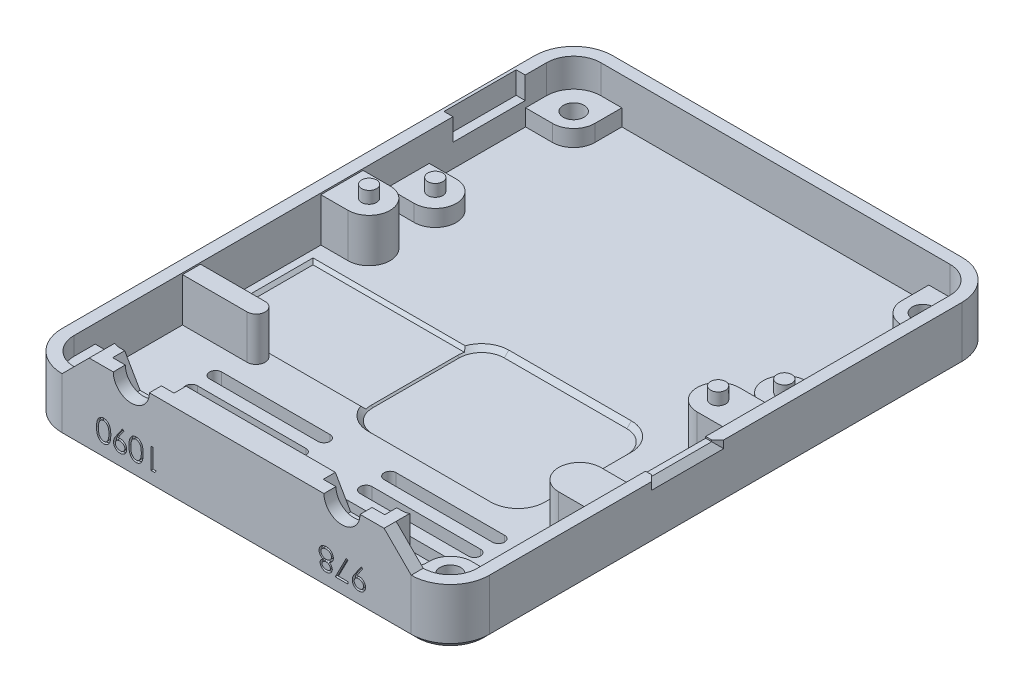
SolidWorks part; units mm, degrees
ref_plane "Front Plane" through (0, 0, 0) normal (0, 0, 1) x (1, 0, 0)
ref_plane "Top Plane" through (0, 0, 0) normal (0, 1, 0) x (1, 0, 0)
ref_plane "Right Plane" through (0, 0, 0) normal (1, 0, 0) x (0, 0, -1)
sketch "Sketch1" plane through (0, 0, 0) normal (0, 1, 0) x (1, 0, 0)
  line L0 (-33.8462, -25.5532) -> (31.1538, -25.5532)
  line L1 (-33.8462, 38.4468) -> (31.1538, 38.4468)
  line L2 (-33.8462, 38.4468) -> (-33.8462, 8.4468)
  line L3 (-33.8462, 8.4468) -> (31.1538, 8.4468)
  line L4 (31.1538, 38.4468) -> (31.1538, 8.4468)
  line L5 (-30.3462, 34.9468) -> (27.6538, 34.9468)
  line L6 (-30.3462, 34.9468) -> (-30.3462, 11.9468)
  line L7 (-30.3462, 11.9468) -> (27.6538, 11.9468)
  line L8 (27.6538, 34.9468) -> (27.6538, 11.9468)
  line L9 (-30.3462, 0.9468) -> (27.6538, 0.9468)
  line L10 (-30.3462, 0.9468) -> (-30.3462, -22.0532)
  line L11 (-33.8462, 4.4468) -> (31.1538, 4.4468)
  line L12 (-33.8462, 4.4468) -> (-33.8462, -25.5532)
  line L13 (-30.3462, -22.0532) -> (27.6538, -22.0532)
  line L14 (31.1538, 4.4468) -> (31.1538, -25.5532)
  line L15 (27.6538, 0.9468) -> (27.6538, -22.0532)
  line L16 (-37.9161, 25.3468) -> (-35.3276, 25.3468)
  line L17 (7.5538, 7.5472) -> (7.5538, 6.2645)
  line L18 (20.1538, 7.5472) -> (20.1538, 6.2645)
  dimension "D1" = 65
  dimension "D2" = 30
  dimension "D3" = 58
  dimension "D4" = 23
  dimension "D5" = 3.5
  dimension "D6" = 3.5
  dimension "D7" = 65
  dimension "D8" = 30
  dimension "D9" = 58
  dimension "D10" = 23
  dimension "D11" = 3.5
  dimension "D12" = 3.5
  dimension "D13" = 4
  dimension "D14" = 16.9
  dimension "D15" = 41.4
  dimension "D16" = 54
sketch "Sketch2" plane through (0, 0, 0) normal (0, 1, 0) x (1, 0, 0)
  line L0 (-33.8462, 38.4468) -> (-33.8462, 8.4468) construction
  line L1 (-30.3462, 39.4468) -> (27.6538, 39.4468)
  line L2 (-34.8462, 34.9468) -> (-34.8462, -43.5532)
  line L3 (-30.3462, -48.0532) -> (27.6538, -48.0532)
  line L4 (32.1538, 34.9468) -> (32.1538, -43.5532)
  line L5 (-33.8462, 38.4468) -> (31.1538, 38.4468) construction
  line L6 (31.1538, 38.4468) -> (31.1538, 8.4468) construction
  line L7 (-30.3462, 41.4468) -> (27.6538, 41.4468)
  line L8 (34.1538, 34.9468) -> (34.1538, -43.5532)
  line L9 (-30.3462, -50.0532) -> (27.6538, -50.0532)
  line L10 (-36.8462, 34.9468) -> (-36.8462, -43.5532)
  line L11 (-34.8462, 39.4468) -> (32.1538, 39.4468) construction
  line L12 (-34.8462, 39.4468) -> (-34.8462, -48.0532) construction
  line L13 (-36.8462, 41.4468) -> (-36.8462, -50.0532) construction
  line L14 (-36.8462, 41.4468) -> (34.1538, 41.4468) construction
  line L15 (32.1538, 39.4468) -> (32.1538, -48.0532) construction
  line L16 (34.1538, 41.4468) -> (34.1538, -50.0532) construction
  line L17 (-36.8462, -50.0532) -> (34.1538, -50.0532) construction
  line L18 (-34.8462, -48.0532) -> (32.1538, -48.0532) construction
  arc A0 (-30.3462, 39.4468) -> (-34.8462, 34.9468) centre (-30.3462, 34.9468) ccw
  arc A1 (-36.8462, 34.9468) -> (-30.3462, 41.4468) centre (-30.3462, 34.9468) cw
  arc A2 (32.1538, 34.9468) -> (27.6538, 39.4468) centre (27.6538, 34.9468) ccw
  arc A3 (34.1538, 34.9468) -> (27.6538, 41.4468) centre (27.6538, 34.9468) ccw
  arc A4 (27.6538, -50.0532) -> (34.1538, -43.5532) centre (27.6538, -43.5532) ccw
  arc A5 (-36.8462, -43.5532) -> (-30.3462, -50.0532) centre (-30.3462, -43.5532) ccw
  arc A6 (27.6538, -48.0532) -> (32.1538, -43.5532) centre (27.6538, -43.5532) ccw
  arc A7 (-30.3462, -48.0532) -> (-34.8462, -43.5532) centre (-30.3462, -43.5532) cw
  dimension "D6" = 4.5
  dimension "D7" = 6.5
  dimension "D8" = 4.5
  dimension "D9" = 6.5
  dimension "D10" = 6.5
  dimension "D11" = 4.5
  dimension "D1" = 1
  dimension "D2" = 1
  dimension "D3" = 1
  dimension "D4" = 87.5
  dimension "D5" = 2
extrude "Boss-Extrude1" add sketch "Sketch2" along normal blind 9.5
sketch "Sketch3" plane through (0, 0, 0) normal (0, 1, 0) x (1, 0, 0)
  line L0 (-30.3462, -48.0532) -> (27.6538, -48.0532)
  line L1 (-30.3462, 39.4468) -> (27.6538, 39.4468)
  line L2 (-34.8462, 34.9468) -> (-34.8462, -43.5532)
  line L4 (32.1538, 34.9468) -> (32.1538, -43.5532)
  arc A0 (-34.8462, -43.5532) -> (-30.3462, -48.0532) centre (-30.3462, -43.5532) ccw
  arc A1 (27.6538, -48.0532) -> (32.1538, -43.5532) centre (27.6538, -43.5532) ccw
  arc A2 (32.1538, 34.9468) -> (27.6538, 39.4468) centre (27.6538, 34.9468) ccw
  arc A3 (-30.3462, 39.4468) -> (-34.8462, 34.9468) centre (-30.3462, 34.9468) ccw
  dimension "D1" = 4.5
  dimension "D2" = 4.5
  dimension "D3" = 87.5
extrude "Boss-Extrude2" add sketch "Sketch3" along normal blind 2
sketch "Sketch4" plane through (0, 2, 0) normal (0, 1, 0) x (1, 0, 0)
  line L1 (-4.1234, -3.5548) -> (16.2444, -3.5548)
  line L2 (-7.1234, -6.5548) -> (-7.1234, -20.9191)
  line L3 (-4.1234, -23.9191) -> (16.2444, -23.9191)
  line L4 (19.2444, -6.5548) -> (19.2444, -20.9191)
  arc A0 (16.2444, -23.9191) -> (19.2444, -20.9191) centre (16.2444, -20.9191) ccw
  arc A1 (-7.1234, -20.9191) -> (-4.1234, -23.9191) centre (-4.1234, -20.9191) ccw
  arc A2 (19.2444, -6.5548) -> (16.2444, -3.5548) centre (16.2444, -6.5548) ccw
  arc A3 (-7.1234, -6.5548) -> (-4.1234, -3.5548) centre (-4.1234, -6.5548) cw
  dimension "D1" = 3
extrude "Cut-Extrude2" cut sketch "Sketch4" against normal blind 0.75
chamfer "Chamfer1" distance 1.5 angle 45 8 edges at (6.0605, 2, 23.9191) (18.3657, 2, 23.0404) (-6.2447, 2, 23.0404) (19.2444, 2, 13.7369) (-7.1234, 2, 13.7369) (18.3657, 2, 4.4335) (-6.2447, 2, 4.4335) (6.0605, 2, 3.5548) tangent propagation no
sketch "Sketch5" plane through (0, 1.25, 0) normal (0, 1, 0) x (1, 0, 0)
  line L0 (-30.3462, 4.4468) -> (-34.8462, 4.4468)
  line L1 (-34.8462, 34.9468) -> (-34.8462, -43.5532) construction
  line L2 (-34.8462, 4.4468) -> (-34.8462, -2.5532)
  line L3 (-34.8462, -2.5532) -> (-30.3462, -2.5532)
  line L4 (27.6538, 4.4468) -> (32.1538, 4.4468)
  line L5 (32.1538, -43.5532) -> (32.1538, 34.9468) construction
  line L6 (32.1538, 4.4468) -> (32.1538, -2.5532)
  line L7 (32.1538, -43.5532) -> (32.1538, 34.9468) construction
  line L8 (32.1538, -2.5532) -> (27.6538, -2.5532)
  line L9 (32.1538, -18.5532) -> (32.1538, -25.5532)
  line L10 (-34.8462, -25.5532) -> (-24.1094, -25.5532)
  line L11 (-34.8462, -25.5532) -> (-34.8462, -22.5532)
  line L12 (-34.8462, -22.5532) -> (-24.1094, -22.5532)
  line L13 (32.1538, -25.5532) -> (27.6538, -25.5532)
  line L14 (27.6538, -18.5532) -> (32.1538, -18.5532)
  arc A0 (-30.3462, -2.5532) -> (-30.3462, 4.4468) centre (-30.3462, 0.9468) ccw
  arc A1 (27.6538, 4.4468) -> (27.6538, -2.5532) centre (27.6538, 0.9468) ccw
  arc A2 (-24.1094, -22.5532) -> (-24.1094, -25.5532) centre (-24.1094, -24.0532) cw
  arc A3 (27.6538, -18.5532) -> (27.6538, -25.5532) centre (27.6538, -22.0532) ccw
  dimension "D1" = 3
extrude "Boss-Extrude3" add sketch "Sketch5" along normal blind 8
sketch "Sketch6" plane through (0, 1.25, 0) normal (0, 1, 0) x (1, 0, 0)
  line L0 (-30.3462, 15.4468) -> (-34.8462, 15.4468)
  line L1 (-34.8462, 34.9468) -> (-34.8462, -43.5532) construction
  line L2 (-34.8462, 15.4468) -> (-34.8462, 8.4468)
  line L3 (-34.8462, 34.9468) -> (-34.8462, 4.4468) construction
  line L4 (-34.8462, 8.4468) -> (-30.3462, 8.4468)
  line L5 (-26.8462, 34.9468) -> (-26.8462, 39.4468)
  line L6 (27.6538, 39.4468) -> (-30.3462, 39.4468) construction
  line L7 (-26.8462, 39.4468) -> (-30.3462, 39.4468)
  line L8 (-30.3462, 31.4468) -> (-34.8462, 31.4468)
  line L9 (-34.8462, 31.4468) -> (-34.8462, 34.9468)
  line L10 (24.1538, 34.9468) -> (24.1538, 39.4468)
  line L11 (24.1538, 39.4468) -> (27.6538, 39.4468)
  line L12 (27.6538, 31.4468) -> (32.1538, 31.4468)
  line L13 (32.1538, 4.4468) -> (32.1538, 34.9468) construction
  line L14 (32.1538, 31.4468) -> (32.1538, 34.9468)
  line L15 (27.6538, 15.4468) -> (32.1538, 15.4468)
  line L16 (27.6538, 8.4468) -> (32.1538, 8.4468)
  line L17 (32.1538, -43.5532) -> (32.1538, 34.9468) construction
  line L18 (32.1538, 8.4468) -> (32.1538, 15.4468)
  arc A0 (-30.3462, 31.4468) -> (-26.8462, 34.9468) centre (-30.3462, 34.9468) ccw
  arc A1 (24.1538, 34.9468) -> (27.6538, 31.4468) centre (27.6538, 34.9468) ccw
  arc A2 (27.6538, 15.4468) -> (27.6538, 8.4468) centre (27.6538, 11.9468) ccw
  arc A3 (-30.3462, 8.4468) -> (-30.3462, 15.4468) centre (-30.3462, 11.9468) ccw
  arc A4 (-30.3462, 39.4468) -> (-34.8462, 34.9468) centre (-30.3462, 34.9468) ccw
  arc A5 (32.1538, 34.9468) -> (27.6538, 39.4468) centre (27.6538, 34.9468) ccw
  dimension "D1" = 4.5
  dimension "D2" = 4.5
extrude "Boss-Extrude4" add sketch "Sketch6" along normal blind 3.5
sketch "Sketch7" plane through (0, 0, 50.0532) normal (0, 0, 1) x (1, 0, 0)
  line L0 (27.6538, 9.5) -> (-30.3462, 9.5)
  line L3 (13.1538, 14) -> (-15.8462, 14)
  line L4 (-1.3462, 9.5) -> (-1.3462, 14) construction
  line L5 (-30.3462, 9.5) -> (27.6538, 9.5) construction
  line L6 (-30.3462, 9.5) -> (-25.8462, 14)
  line L7 (-25.8462, 14) -> (-21.8462, 14)
  line L9 (23.1538, 14) -> (19.1538, 14)
  line L13 (27.6538, 9.5) -> (23.1538, 14)
  arc A0 (-21.8462, 14) -> (-15.8462, 14) centre (-18.8462, 14) ccw
  arc A1 (13.1538, 14) -> (19.1538, 14) centre (16.1538, 14) ccw
  dimension "D2" = 35
  dimension "D1" = 4.5
  dimension "D6" = 3
  dimension "D7" = 3
  dimension "D3" = 4.5
  dimension "D4" = 45
  dimension "D5" = 4.5
extrude "Boss-Extrude5" add sketch "Sketch7" against normal up to vertex (2 mm away) up to point (-30.3462, 9.5, 48.0532)
sketch "Sketch10" plane through (0, 2, 0) normal (0, 1, 0) x (1, 0, 0)
  line L0 (-30.3462, -40.0532) -> (-34.8462, -40.0532)
  line L1 (27.6538, -40.0532) -> (32.1538, -40.0532)
  line L2 (-34.8462, -40.0532) -> (-34.8462, -43.5532)
  line L3 (-26.8462, -43.5532) -> (-26.8462, -48.0532)
  line L4 (32.1538, -43.5532) -> (32.1538, 34.9468) construction
  line L5 (-26.8462, -48.0532) -> (-30.3462, -48.0532)
  line L6 (32.1538, -40.0532) -> (32.1538, -43.5532)
  line L7 (24.1538, -43.5532) -> (24.1538, -48.0532)
  line L8 (-30.3462, -48.0532) -> (27.6538, -48.0532) construction
  line L9 (24.1538, -48.0532) -> (27.6538, -48.0532)
  line L10 (-4.8462, -43.5532) -> (-4.8462, -48.0532)
  line L11 (-4.8462, -48.0532) -> (2.1538, -48.0532)
  line L12 (2.1538, -48.0532) -> (2.1538, -43.5532)
  arc A0 (-34.8462, -43.5532) -> (-30.3462, -48.0532) centre (-30.3462, -43.5532) ccw
  arc A1 (-26.8462, -43.5532) -> (-30.3462, -40.0532) centre (-30.3462, -43.5532) ccw
  arc A2 (32.1538, -43.5532) -> (27.6538, -48.0532) centre (27.6538, -43.5532) cw
  arc A3 (27.6538, -48.0532) -> (32.1538, -43.5532) centre (27.6538, -43.5532) ccw construction
  arc A4 (27.6538, -40.0532) -> (24.1538, -43.5532) centre (27.6538, -43.5532) ccw
  arc A5 (2.1538, -43.5532) -> (-4.8462, -43.5532) centre (-1.3462, -43.5532) ccw
extrude "Boss-Extrude6" add sketch "Sketch10" along normal offset from surface (4.5 mm away) 3 up to face at (-1.3462, 9.5, 4.3032)
sketch "Sketch11" plane through (34.1538, 0, 0) normal (1, 0, 0) x (0, 0, -1)
  line L1 (-15.6251, 10.2426) -> (-5.6251, 10.2426)
  line L2 (-15.6251, 10.2426) -> (-15.6251, 9.2424)
  line L3 (-15.6251, 9.2424) -> (-5.6251, 9.2424)
  line L4 (-5.6251, 10.2426) -> (-5.6251, 9.2424)
extrude "Cut-Extrude3" cut sketch "Sketch11" against normal up to next
chamfer "Chamfer2" distance 1 angle 45 3 edges at (34.1538, 9.3712, 5.6251) (34.1538, 9.3712, 15.6251) (34.1538, 9.2424, 10.6251)
sketch "Sketch12" plane through (-34.8462, 0, 0) normal (-1, 0, 0) x (0, 0, 1)
  line L1 (-31.3918, 9.8223) -> (-19.3918, 9.8223)
  line L2 (-31.3918, 9.8223) -> (-31.3918, 5.8223)
  line L3 (-31.3918, 5.8223) -> (-19.3918, 5.8223)
  line L4 (-19.3918, 9.8223) -> (-19.3918, 5.8223)
  line L5 (-31.3918, 9.8223) -> (-19.3918, 5.8223) construction
  line L6 (-31.3918, 5.8223) -> (-19.3918, 9.8223) construction
  point P0 (-25.3918, 7.8223)
  dimension "D1" = 12
  dimension "D2" = 4
chamfer "Chamfer4" distance 1 angle 45 8 edges at (34.1538, 0, 4.3032) (32.25, 0, -39.543) (32.25, 0, 48.1493) (-1.3462, 0, -41.4468) (-1.3462, 0, 50.0532) (-34.9423, 0, -39.543) (-34.9423, 0, 48.1493) (-36.8462, 0, 4.3032)
sketch "Sketch34" plane through (0, 2, 0) normal (0, 1, 0) x (1, 0, 0)
  line L1 (-5.843, -6.5548) -> (-32.1578, -6.5548)
  line L2 (-5.843, -6.5548) -> (-5.843, -20.9191)
  line L3 (-5.843, -20.9191) -> (-32.1578, -20.9191)
  line L4 (-32.1578, -6.5548) -> (-32.1578, -20.9191)
extrude "Cut-Extrude5" cut sketch "Sketch34" against normal blind 0.5
chamfer "Chamfer5" distance 1.5 angle 45 3 edges at (-20.3906, 2, 20.9191) (-32.1578, 2, 13.7369) (-20.3906, 2, 6.5548)
extrude "Cut-Extrude6" cut sketch "Sketch12" along normal blind 1.5
sketch "Sketch36" plane through (0, 0, 0) normal (0, -1, 0) x (1, 0, 0)
  line L0 (-5.6411, -4.4361) -> (-6.5788, -2.9987)
  line L1 (-5.6135, -17.5484) -> (-6.5451, -18.9896)
  line L2 (2.8733, -4.4181) -> (3.8048, -2.9769)
  line L3 (2.9009, -17.5304) -> (3.8385, -18.9678)
  line L4 (-14.7411, -31.67) -> (-15.5841, -32.9742)
  line L5 (-9.464, -23.5056) -> (-10.3585, -24.8894)
  line L6 (-9.5167, 1.5049) -> (-10.4169, 2.885)
  line L7 (-14.8281, 9.647) -> (-15.6766, 10.9477)
  line L8 (12.0008, 9.7035) -> (12.8438, 11.0078)
  line L9 (6.7238, 1.5391) -> (7.6182, 2.9229)
  line L10 (6.7764, -23.4714) -> (7.6767, -24.8515)
  line L11 (12.0878, -31.6135) -> (12.9363, -32.9142)
  line L12 (-3.5903, -40.4468) -> (-2.2438, -13.3244)
  line L13 (0.898, -40.4468) -> (-0.192, -13.3244)
  line L14 (-3.5903, -40.4468) -> (0.898, -40.4468)
  line L15 (-2.2438, -13.3244) -> (-0.192, -13.3244)
  arc A0 (12.9363, -32.9142) -> (12.8438, 11.0078) centre (-1.3701, -10.9832) ccw
  arc A1 (12.0878, -31.6135) -> (12.0008, 9.7035) centre (-1.3701, -10.9832) ccw
  arc A2 (2.9009, -17.5304) -> (2.8733, -4.4181) centre (-1.3701, -10.9832) ccw
  arc A3 (3.8385, -18.9678) -> (3.8048, -2.9769) centre (-1.3701, -10.9832) ccw
  arc A4 (7.6767, -24.8515) -> (7.6182, 2.9229) centre (-1.3701, -10.9832) ccw
  arc A5 (6.7764, -23.4714) -> (6.7238, 1.5391) centre (-1.3701, -10.9832) ccw
  arc A6 (-15.6766, 10.9477) -> (-15.5841, -32.9742) centre (-1.3701, -10.9832) ccw
  arc A7 (-14.8281, 9.647) -> (-14.7411, -31.67) centre (-1.3701, -10.9832) ccw
  arc A8 (-10.4169, 2.885) -> (-10.3585, -24.8894) centre (-1.3701, -10.9832) ccw
  arc A9 (-9.5167, 1.5049) -> (-9.464, -23.5056) centre (-1.3701, -10.9832) ccw
  arc A10 (-6.5788, -2.9987) -> (-6.5451, -18.9896) centre (-1.3701, -10.9832) ccw
  arc A11 (-5.6411, -4.4361) -> (-5.6135, -17.5484) centre (-1.3701, -10.9832) ccw
extrude "Cut-Extrude8" cut sketch "Sketch36" against normal blind 0.4
sketch "Sketch37" plane through (0, 0, 0) normal (0, 1, 0) x (1, 0, 0)
  line L0 (-1.9008, 5.7134) -> (12.3211, -8.0776)
  line L1 (12.3211, -8.0776) -> (16.1409, -4.1385)
  line L2 (16.1409, -4.1385) -> (3.4609, 11.2426)
  line L3 (3.4609, 11.2426) -> (9.8009, 20.3663)
  line L4 (9.8009, 20.3663) -> (15.1149, 16.2462)
  line L5 (15.1149, 16.2462) -> (17.8041, 19.0194)
  line L6 (17.8041, 19.0194) -> (12.774, 24.201)
  line L7 (12.774, 24.201) -> (13.7731, 25.4896)
  line L8 (13.7731, 25.4896) -> (13.4862, 25.712)
  line L9 (-1.9008, 5.7134) -> (-4.5225, 3.5521)
  line L10 (-4.5225, 3.5521) -> (-6.7547, 2.0307)
  line L11 (-6.7547, 2.0307) -> (-8.3897, 1.1526)
  line L12 (-8.3897, 1.1526) -> (-9.0215, 1.5916)
  line L13 (-9.0215, 1.5916) -> (-9.9767, 1.0787)
  line L14 (-9.9767, 1.0787) -> (-10.839, 0.7913)
  line L15 (-10.839, 0.7913) -> (-11.0799, 0.7913)
  line L16 (13.4862, 25.712) -> (-11.0799, 0.7913) construction
  line L17 (-11.0833, 1.0321) -> (-11.0799, 0.7913)
  line L18 (-10.8083, 1.8985) -> (-11.0833, 1.0321)
  line L19 (-10.3091, 2.8609) -> (-10.8083, 1.8985)
  line L20 (-10.7571, 3.4863) -> (-10.3091, 2.8609)
  line L21 (-9.9026, 5.1337) -> (-10.7571, 3.4863)
  line L22 (-8.4134, 7.3875) -> (-9.9026, 5.1337)
  line L23 (-6.2899, 10.0399) -> (-8.4134, 7.3875)
  line L24 (13.2596, 25.9958) -> (13.4862, 25.712)
  line L25 (11.9855, 24.9783) -> (13.2596, 25.9958)
  line L26 (6.7323, 29.9336) -> (11.9855, 24.9783)
  line L27 (3.9979, 27.2049) -> (6.7323, 29.9336)
  line L28 (8.1938, 21.9505) -> (3.9979, 27.2049)
  line L29 (-0.8381, 15.4803) -> (8.1938, 21.9505)
  line L30 (-16.3994, 27.9385) -> (-0.8381, 15.4803)
  line L31 (-20.2833, 24.0627) -> (-16.3994, 27.9385)
  line L32 (-6.2899, 10.0399) -> (-20.2833, 24.0627)
extrude "Cut-Extrude14" cut sketch "Sketch37" along normal blind 0.4
sketch "Sketch38" plane through (0, 0, 48.0532) normal (0, 0, -1) x (-1, 0, 0)
  line L0 (-23.1538, 14) -> (-21.2558, 14)
  line L1 (-23.1538, 14) -> (-23.1538, 6.5)
  line L2 (16.2952, 9.5816) -> (21.3971, 9.5816)
  line L3 (26.8462, 2) -> (4.8462, 2) construction
  line L4 (-21.2558, 14) -> (-18.7048, 9.5816)
  line L5 (-18.7048, 9.5816) -> (-13.6029, 9.5816)
  line L6 (-13.6029, 9.5816) -> (-11.0519, 14)
  line L7 (-23.9027, 2) -> (-9.4512, 2)
  line L8 (21.3971, 9.5816) -> (23.9481, 14)
  line L9 (-19.9803, 16.2092) -> (-21.135, 14.2092) [skipped]
  line L10 (-14.8081, 18.4184) -> (-17.1175, 18.4184) [skipped]
  line L11 (-12.3274, 16.2092) -> (-13.4821, 18.2092) [skipped]
  line L12 (13.7442, 14) -> (16.2952, 9.5816)
  line L13 (25.8462, 14) -> (23.9481, 14)
  line L15 (13.7442, 14) -> (12.1436, 14)
  line L16 (-9.4512, 14) -> (12.1436, 14)
  line L17 (26.8462, 6.5) -> (25.8462, 6.5)
  line L18 (-24.1538, 6.5) -> (-23.1538, 6.5)
  line L20 (-9.4512, 14) -> (-11.0519, 14)
  line L22 (-24.1538, 6.5) -> (-24.1538, 2)
  line L23 (-24.1538, 2) -> (-23.9027, 2)
  line L25 (25.8462, 14) -> (25.8462, 6.5)
  line L27 (26.8462, 6.5) -> (26.8462, 2)
  line L28 (26.8462, 2) -> (-9.4512, 2)
  arc A0 (15.3313, 11.2512) -> (22.361, 11.2512) centre (18.8462, 14) ccw construction
  arc A2 (-19.6687, 11.2512) -> (-12.639, 11.2512) centre (-16.1538, 14) ccw construction
extrude "Boss-Extrude7" add sketch "Sketch38" along normal blind 2
sketch "Sketch39" plane through (0, 0, 50.0532) normal (0, 0, 1) x (1, 0, 0)
  line L0 (-25.8321, 6.4571) -> (-13.0275, 6.4571) construction
  line L1 (9.3531, 6.4571) -> (23.0562, 6.4571) construction
  text T0 "1090"
  text T1 "978"
extrude "Cut-Extrude15" cut sketch "Sketch39" against normal blind 0.5
sketch "Sketch40" plane through (0, 4.75, 0) normal (0, 1, 0) x (1, 0, 0)
  circle A0 centre (-30.3462, 11.9468) radius 1.25
  circle A1 centre (27.6538, 11.9468) radius 1.25
  dimension "D1" = 2.5
  dimension "D2" = 2.5
extrude "Boss-Extrude8" add sketch "Sketch40" along normal blind 2
sketch "Sketch41" plane through (0, 9.25, 0) normal (0, 1, 0) x (1, 0, 0)
  circle A0 centre (-30.3462, 0.9468) radius 1.25
  circle A2 centre (27.6538, 0.9468) radius 1.25
  dimension "D1" = 2.5
  dimension "D2" = 2.5
extrude "Boss-Extrude9" add sketch "Sketch41" along normal blind 2
fillet "Fillet1" radius 2 6 edges at (13.1538, 2, 46.0532) (-15.8462, 2, 46.0532) (-4.8462, 4.25, 46.0532) (24.1538, 4.25, 46.0532) (2.1538, 4.25, 46.0532) (-26.8462, 4.25, 46.0532)
hole_wizard "CSK for #4 Flat Head Socket Cap Screw1" positions "Sketch43" profile "Sketch42" countersink size "#4" standard "ANSI Inch" end condition through all
sketch "Sketch43" plane through (0, 0, 0) normal (0, -1, 0) x (-1, 0, 0)
  point P2 (30.3462, -43.5532)
  point P6 (1.3462, -43.5532)
  point P10 (-27.6538, -43.5532)
  point P14 (30.3462, 34.9468)
  point P18 (-27.6538, 34.9468)
sketch "Sketch42" plane through (-30.3462, 0, 43.5532) normal (1, 0, 0) x (0, 0, -1)
  line L0 (0, 0) -> (0, 14)
  line L1 (0, 14) -> (1.7272, 14)
  line L2 (1.7272, 14) -> (1.7272, 1.8805)
  line L3 (1.7272, 1.8805) -> (3.3619, 0)
  line L5 (3.3619, 0) -> (0, 0)
  line L6 (-1.7272, 1.8805) -> (-3.3619, 0) construction
  line L11 (0, -6.35) -> (0, 107.95) construction
  dimension "Thru Hole Dia." = 3.4544
  dimension "Thru Hole Depth" = 14
  dimension "Near C'Sink Dia." = 6.7237
  dimension "Near C'Sink Angle" = 82
sketch "Sketch44" plane through (0, 2, 0) normal (0, 1, 0) x (1, 0, 0)
  line L0 (-24.8462, -38.0532) -> (-6.8462, -38.0532) construction
  line L1 (-24.8462, -37.0532) -> (-6.8462, -37.0532)
  line L2 (-24.8462, -39.0532) -> (-6.8462, -39.0532)
  line L3 (-6.8462, -46.0532) -> (-24.8462, -46.0532) construction
  line L4 (-24.8462, -34.0532) -> (-6.8462, -34.0532) construction
  line L5 (-24.8462, -33.0532) -> (-6.8462, -33.0532)
  line L6 (-24.8462, -35.0532) -> (-6.8462, -35.0532)
  line L7 (-24.8462, -30.0532) -> (-6.8462, -30.0532) construction
  line L8 (-24.8462, -29.0532) -> (-6.8462, -29.0532)
  line L9 (-24.8462, -31.0532) -> (-6.8462, -31.0532)
  line L10 (4.1538, -38.0532) -> (22.1538, -38.0532) construction
  line L11 (4.1538, -37.0532) -> (22.1538, -37.0532)
  line L12 (4.1538, -39.0532) -> (22.1538, -39.0532)
  line L13 (4.1538, -34.0532) -> (22.1538, -34.0532) construction
  line L14 (4.1538, -33.0532) -> (22.1538, -33.0532)
  line L15 (4.1538, -35.0532) -> (22.1538, -35.0532)
  line L16 (4.1538, -30.0532) -> (22.1538, -30.0532) construction
  line L17 (4.1538, -29.0532) -> (22.1538, -29.0532)
  line L18 (4.1538, -31.0532) -> (22.1538, -31.0532)
  arc A0 (-24.8462, -37.0532) -> (-24.8462, -39.0532) centre (-24.8462, -38.0532) ccw
  arc A1 (-6.8462, -39.0532) -> (-6.8462, -37.0532) centre (-6.8462, -38.0532) ccw
  arc A2 (-24.8462, -33.0532) -> (-24.8462, -35.0532) centre (-24.8462, -34.0532) ccw
  arc A3 (-6.8462, -35.0532) -> (-6.8462, -33.0532) centre (-6.8462, -34.0532) ccw
  arc A4 (-24.8462, -29.0532) -> (-24.8462, -31.0532) centre (-24.8462, -30.0532) ccw
  arc A5 (-6.8462, -31.0532) -> (-6.8462, -29.0532) centre (-6.8462, -30.0532) ccw
  arc A6 (4.1538, -37.0532) -> (4.1538, -39.0532) centre (4.1538, -38.0532) ccw
  arc A7 (22.1538, -39.0532) -> (22.1538, -37.0532) centre (22.1538, -38.0532) ccw
  arc A8 (4.1538, -33.0532) -> (4.1538, -35.0532) centre (4.1538, -34.0532) ccw
  arc A9 (22.1538, -35.0532) -> (22.1538, -33.0532) centre (22.1538, -34.0532) ccw
  arc A10 (4.1538, -29.0532) -> (4.1538, -31.0532) centre (4.1538, -30.0532) ccw
  arc A11 (22.1538, -31.0532) -> (22.1538, -29.0532) centre (22.1538, -30.0532) ccw
  point P2 (-15.8462, -38.0532)
  point P12 (-15.8462, -34.0532)
  point P19 (-15.8462, -30.0532)
  point P25 (13.1538, -38.0532)
  point P32 (13.1538, -34.0532)
  point P39 (13.1538, -30.0532)
  dimension "D1" = 8
  dimension "D2" = 3
extrude "Cut-Extrude16" cut sketch "Sketch44" against normal through all
